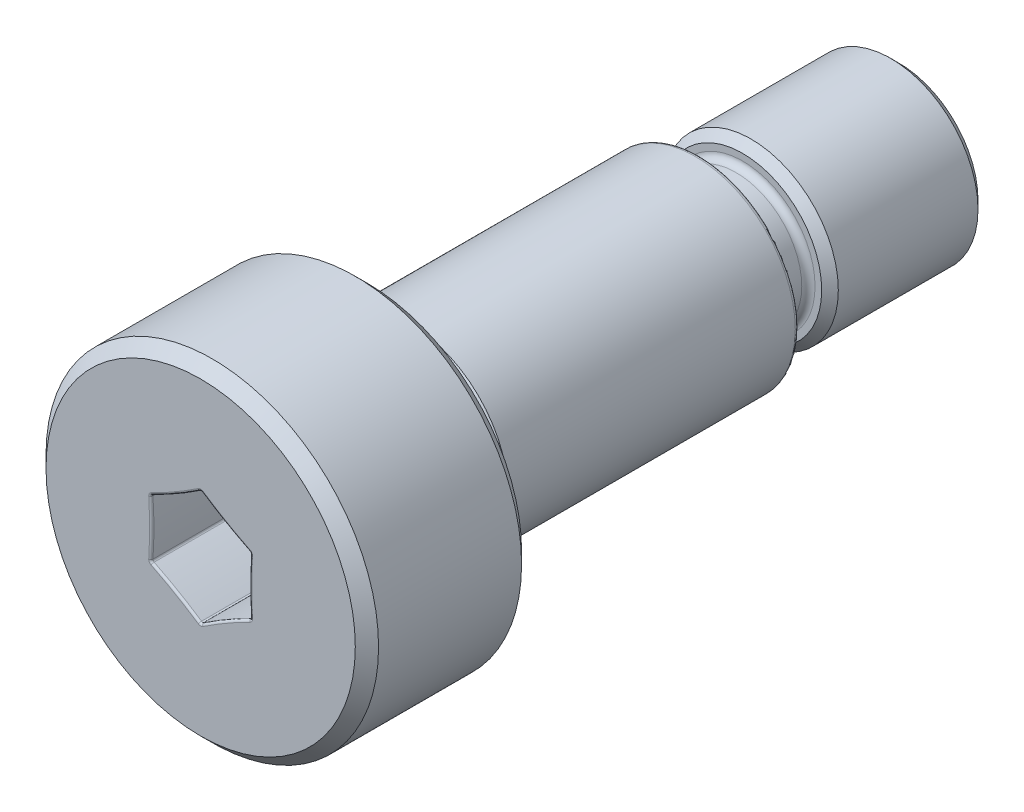
SolidWorks part; units mm, degrees
material "Alloy Steel (SS)"
ref_plane "Front Plane" through (0, 0, 0) normal (0, 0, 1) x (1, 0, 0)
ref_plane "Top Plane" through (0, 0, 0) normal (0, 1, 0) x (1, 0, 0)
ref_plane "Right Plane" through (0, 0, 0) normal (1, 0, 0) x (0, 0, -1)
sketch "Sketch1" plane through (0, 0, 0) normal (0, 0, 1) x (1, 0, 0)
  line L1 (1.1906, 0.6874) -> (0, 1.3748)
  line L2 (0, 1.3748) -> (-1.1906, 0.6874)
  line L3 (-1.1906, 0.6874) -> (-1.1906, -0.6874)
  line L4 (-1.1906, -0.6874) -> (0, -1.3748)
  line L5 (0, -1.3748) -> (1.1906, -0.6874)
  line L6 (1.1906, -0.6874) -> (1.1906, 0.6874)
  circle A0 centre (0, 0) radius 3.9688
  circle A1 centre (0, 0) radius 2.3813
  circle A2 centre (0, 0) radius 2.0828
  circle A3 centre (0, 0) radius 1.1906 construction
  dimension "Head Diameter" = 7.9375
  dimension "Shoulder Diameter" = 4.7625
  dimension "Screw Size Decimal Equivalent" = 4.1656
  dimension "Drive Size" = 2.3813
sketch "Sketch2" plane through (0, 0, 0) normal (1, 0, 0) x (0, 0, -1)
  line L0 (12.7, 2.0828) -> (0, 2.0828) construction
  line L1 (0, 3.9688) -> (-3.9688, 3.9687) construction
  line L2 (7.9375, 2.3813) -> (0, 2.3813) construction
  line L3 (0, -3.9688) -> (-3.9688, -3.9688) construction
  line L6 (0, -2.0828) -> (12.7, -2.0828) construction
  line L9 (12.6504, 2.1687) -> (13.4441, 2.1687) construction
  line L10 (13.4441, 2.1687) -> (13.0473, 1.4813) construction
  line L11 (13.0473, 1.4813) -> (12.6504, 2.1687) construction
  line L12 (12.7, 2.0828) -> (13.3945, 2.0828) construction
  line L13 (12.9977, 1.5672) -> (13.0969, 1.5672) construction
  line L14 (13.0473, 1.5672) -> (13.0473, 1.4813) construction
  line L15 (13.0473, 2.1687) -> (13.0473, 2.0828) construction
  line L16 (12.6752, 2.1258) -> (13.4193, 2.1258) construction
  line L17 (-3.9688, 0) -> (12.7, 0) construction
  line L18 (7.9375, 2.3813) -> (7.9375, -2.0828) construction
  point P23 (13.0473, 2.1258)
  point P24 (11.9062, 2.0828)
  dimension "Head Height" = 3.9688
  dimension "Shoulder Length" = 7.9375
  dimension "Thread Length" = 4.7625
  dimension "Thread Pitch" = 0.7937
  dimension "D2" = 0.0992
  dimension "Thread Note" = 0.7937
sketch "Sketch3" plane through (0, 0, 0) normal (1, 0, 0) x (0, 0, -1)
  line L0 (-3.9688, 3.9687) -> (0, 3.9688)
  line L1 (0, 3.9688) -> (0, 2.3813)
  line L2 (0, 2.3813) -> (7.9375, 2.3813)
  line L3 (7.9375, 2.3813) -> (7.9375, 2.0828)
  line L4 (12.7, 2.0828) -> (0, 2.0828) construction
  line L5 (7.9375, 2.0828) -> (12.7, 2.0828)
  line L6 (12.7, 2.0828) -> (12.7, 0)
  line L7 (12.7, 0) -> (-3.9688, 0)
  line L8 (-3.9688, 0) -> (-3.9688, 3.9687)
  line L9 (-3.9688, 0) -> (12.7, 0) construction
revolve "Revolve1" add sketch "Sketch3" angle 360 about L17
sketch "Sketch4" plane through (0, 0, 0) normal (1, 0, 0) x (0, 0, -1)
  line L0 (-3.9688, 0) -> (12.7, 0) construction
  line L1 (0, 2.3813) -> (0.9922, 2.3813)
  line L2 (0, 2.3813) -> (0, 2.0241)
  line L3 (0, 2.0241) -> (0.9922, 2.0241)
  line L4 (0.9922, 2.3813) -> (0.9922, 2.0241)
  line L5 (12.7, 2.0828) -> (0, 2.0828) construction
  line L6 (7.9375, 2.0828) -> (8.9694, 2.0828)
  line L7 (7.9375, 2.0828) -> (7.9375, 1.5672)
  line L8 (7.9375, 1.5672) -> (8.9694, 1.5672)
  line L9 (8.9694, 2.0828) -> (8.9694, 1.5672)
  line L10 (12.9977, 1.5672) -> (13.0969, 1.5672) construction
  line L12 (3.9688, 2.3813) -> (3.9688, 0) construction
  line L13 (7.9375, 2.3813) -> (0, 2.3813) construction
  point P22 (1.2898, 2.0241)
  point P23 (6.6477, 2.0241)
  dimension "D1" = 0.9922
  dimension "D2" = 4.0481
  dimension "D3" = 1.0319
  dimension "D4" = 5.3578
revolve "Cut-Revolve1" cut sketch "Sketch4" angle 360 about L17
chamfer "Chamfer1" distance 0.3572 angle 45 1 edges at (2.0241, 0, -0.9922)
fillet "Fillet1" radius 0.1786 1 edges at (2.0241, 0, 0)
fillet "Fillet2" radius 0.1588 2 edges at (1.5672, 0, -7.9375) (1.5672, 0, -8.9694)
chamfer "Chamfer2" distance 0.1984 angle 45 2 edges at (2.0828, 0, -8.9694) (2.0828, 0, -12.7)
fillet "Fillet3" radius 0.0953 1 edges at (2.3813, 0, -7.9375)
chamfer "Chamfer3" distance 0.2778 angle 45 2 edges at (3.9688, 0, 0) (3.9687, 0, 3.9688)
sketch "Sketch5" plane through (0, 0, 3.9688) normal (0, 0, 1) x (1, 0, 0)
  arc A0 (1.1906, 0.6874) -> (0, 1.3748) centre (5.5503, 9.6134) cw
  circle A2 centre (0, 0) radius 1.1668 construction
  arc A3 (1.1906, -0.6874) -> (1.1906, 0.6874) centre (11.1006, 0) cw
  arc A4 (0, -1.3748) -> (1.1906, -0.6874) centre (5.5503, -9.6134) cw
  arc A5 (-1.1906, -0.6874) -> (0, -1.3748) centre (-5.5503, -9.6134) cw
  arc A6 (-1.1906, 0.6874) -> (-1.1906, -0.6874) centre (-11.1006, 0) cw
  arc A7 (0, 1.3748) -> (-1.1906, 0.6874) centre (-5.5503, 9.6134) cw
  point P25 (0, 0)
  dimension "D1" = 2.3336
  dimension "D2" = 6
extrude "Cut-Extrude1" cut sketch "Sketch5" against normal blind 2.0828
fillet "Fillet4" radius 0.0508 18 edges at (1.1668, 0, 3.9688) (1.1906, -0.6874, 2.9274) (0.5834, -1.0105, 3.9688) (0, -1.3748, 2.9274) (-0.5834, -1.0105, 3.9688) (-1.1906, -0.6874, 2.9274) (-1.1668, 0, 3.9688) (-1.1906, 0.6874, 2.9274) (-0.5834, 1.0105, 3.9688) (1.1906, 0.6874, 2.9274) (0, 1.3748, 2.9274) (0.5834, 1.0105, 3.9688) (0.5834, -1.0105, 1.886) (-0.5834, -1.0105, 1.886) (-1.1668, 0, 1.886) (-0.5834, 1.0105, 1.886) (0.5834, 1.0105, 1.886) (1.1668, 0, 1.886)
sketch "Sketch6" [suppressed] plane through (0, 0, -12.7) normal (0, 0, -1) x (-1, 0, 0)
  circle A0 centre (0, 0) radius 2.0828
  circle A1 centre (0, 0) radius 2.0828 construction
sketch "Sketch7" [suppressed] plane through (0, 0, 0) normal (1, 0, 0) x (0, 0, -1)
  line L0 (12.6752, 2.1258) -> (13.4193, 2.1258)
  line L1 (13.4193, 2.1258) -> (13.0969, 1.5672)
  line L2 (13.0969, 1.5672) -> (12.9977, 1.5672)
  line L3 (12.9977, 1.5672) -> (12.6752, 2.1258)
other "DeleteFace1" [suppressed]
curve "Helix/Spiral1" [suppressed] pitch 0.7937 height 4.3497 turns 5.48
sweep "Cut-Sweep1" [suppressed] cut profiles "Sketch7" path "Helix/Spiral1"
equation "\"D2@Sketch2\" = \"Thread Pitch@Sketch2\" / 8"
equation "\"D1@Sketch4\" = \"Head Height@Sketch2\" * .25"
equation "\"D3@Sketch4\" = \"Thread Pitch@Sketch2\" * 1.3"
equation "\"D2@Sketch4\" = \"Shoulder Diameter@Sketch1\" * .85"
equation "\"D1@Chamfer1\" =  ( \"Shoulder Diameter@Sketch1\" - \"D2@Sketch4\" )  * .5"
equation "\"D1@Fillet1\"=\"d1@chaMFER1\"*.5"
equation "\"D1@Fillet2\"=\"Thread Pitch@Sketch2\"*.2"
equation "\"D1@Chamfer2\"=\"Thread Pitch@Sketch2\"*.25"
equation "\"D1@Fillet3\"=\"Shoulder Diameter@Sketch1\"*.02"
equation "\"D1@Chamfer3\" = \"Head Height@Sketch2\" * .07"
equation "\"D1@Sketch5\"=\"Drive Size@Sketch1\"*.98"
equation "\"D1@Cut-Extrude1\"=\"Screw Size Decimal Equivalent@Sketch1\"*.5"
equation "\"D4@Helix/Spiral1\"=\"thread pitch@sketch2\""
equation "\"D3@Helix/Spiral1\"=\"Thread Length@Sketch2\" - \"D3@Sketch4\" * .4"
equation "\"D4@Sketch4\"=(\"Shoulder Length@Sketch2\"-(2*\"D1@Sketch4\"))*.9"
equation "\"Thread Note@Sketch2\"=\"Thread Pitch@Sketch2\" * 1"
